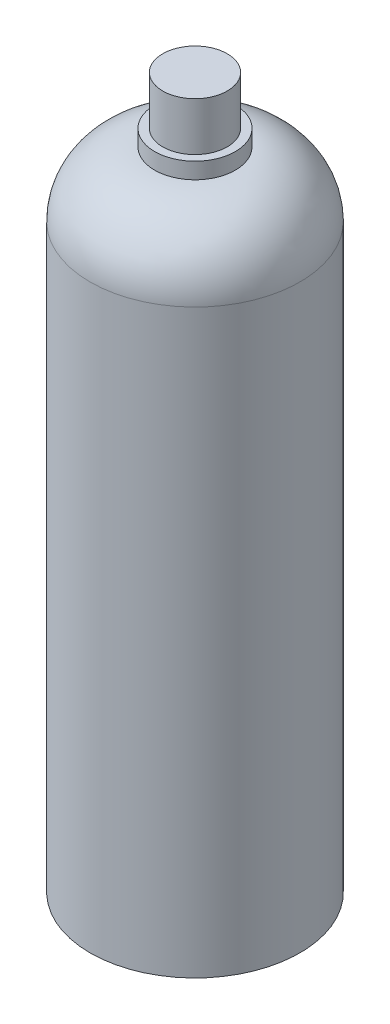
SolidWorks part; units mm, degrees
ref_plane "정면" through (0, 0, 0) normal (0, 0, 1) x (1, 0, 0)
ref_plane "윗면" through (0, 0, 0) normal (0, 1, 0) x (1, 0, 0)
ref_plane "우측면" through (0, 0, 0) normal (1, 0, 0) x (0, 0, -1)
sketch "스케치1" plane through (0, 0, 0) normal (0, 1, 0) x (1, 0, 0)
  circle A0 centre (0, 0) radius 32.5
  dimension "D1" = 65
extrude "보스-돌출1" add sketch "스케치1" along normal blind 200
fillet "필렛1" radius 20 1 edges at (0, 200, 32.5)
sketch "스케치2" plane through (0, 200, 0) normal (0, 1, 0) x (1, 0, 0)
  circle A0 centre (0, 0) radius 10
  circle A1 centre (0, 0) radius 12.5 construction
  circle A2 centre (0, 0) radius 12.5
  dimension "D1" = 20
extrude "보스-돌출2" add sketch "스케치2" along normal blind 20 contours A0
sketch "스케치3" plane through (0, 0, 0) normal (0, 0, 1) x (1, 0, 0)
  line L0 (10, 220) -> (-10, 220) construction
  circle A0 centre (0, 215) radius 2.5
  dimension "D2" = 5
  dimension "D1" = 5
extrude "컷-돌출1" cut sketch "스케치3" along normal blind 2 from offset 10 offset against normal yes
extrude "보스-돌출3" add sketch "스케치2<3>" along normal blind 5
sketch "스케치2<3>" plane through (0, 200, 0) normal (0, 1, 0) x (1, 0, 0) same geometry as "스케치2"
